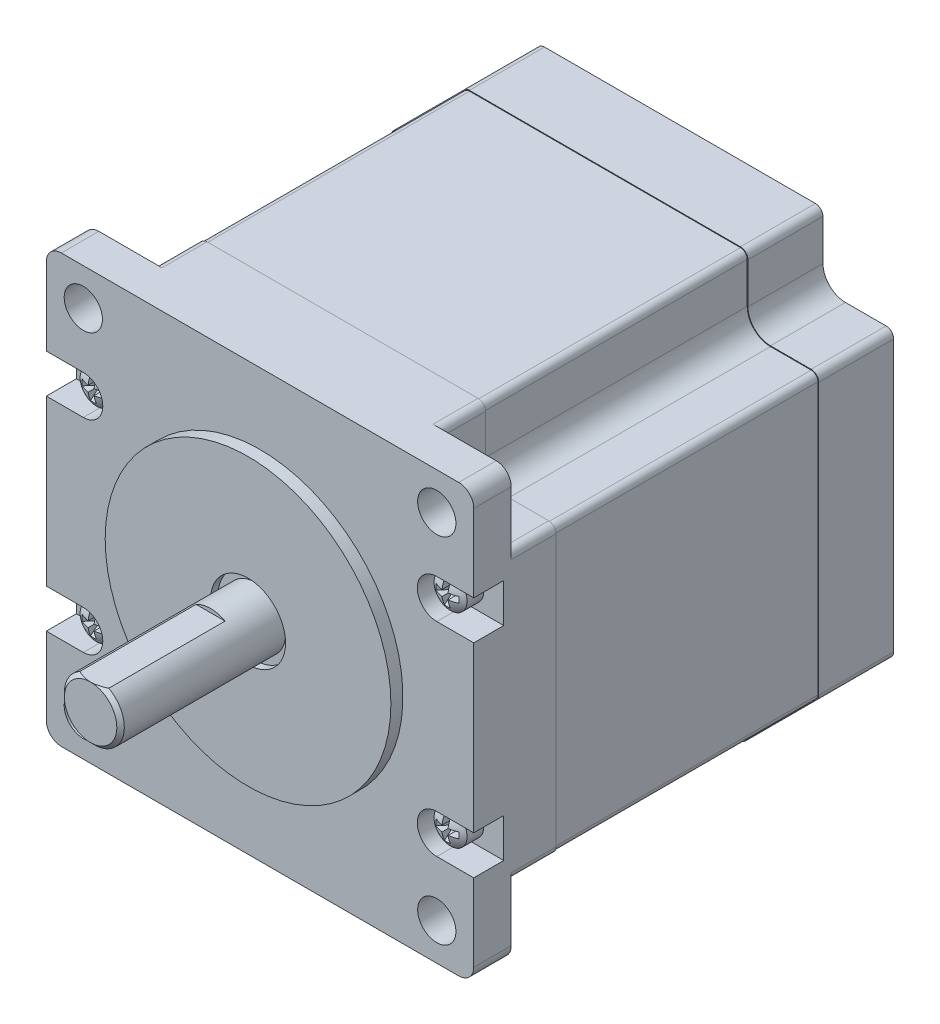
SolidWorks part; units mm, degrees
material "Liga 1060"
ref_plane "Plano frontal" through (0, 0, 0) normal (0, 0, 1) x (1, 0, 0)
ref_plane "Plano superior" through (0, 0, 0) normal (0, 1, 0) x (1, 0, 0)
ref_plane "Plano direito" through (0, 0, 0) normal (1, 0, 0) x (0, 0, -1)
sketch "Esboço1" plane through (0, 0, 0) normal (0, 0, 1) x (1, 0, 0)
  line L1 (-26.5, -28.5) -> (26.5, -28.5)
  line L2 (-28.5, -26.5) -> (-28.5, 26.5)
  line L3 (-26.5, 28.5) -> (26.5, 28.5)
  line L4 (28.5, -26.5) -> (28.5, 26.5)
  line L5 (-28.5, -28.5) -> (28.5, 28.5) construction
  line L6 (-28.5, 28.5) -> (28.5, -28.5) construction
  arc A0 (-26.5, -28.5) -> (-28.5, -26.5) centre (-26.5, -26.5) cw
  arc A1 (26.5, -28.5) -> (28.5, -26.5) centre (26.5, -26.5) ccw
  arc A2 (26.5, 28.5) -> (28.5, 26.5) centre (26.5, 26.5) cw
  arc A3 (-28.5, 26.5) -> (-26.5, 28.5) centre (-26.5, 26.5) cw
  point P0 (0, 0)
  dimension "D1" = 2
  dimension "D2" = 57
extrude "Ressalto-extrusão1" add sketch "Esboço1" along normal blind 5
sketch "Esboço2" plane through (0, 0, 5) normal (0, 0, 1) x (1, 0, 0)
  line L0 (-28.5, 0) -> (0, 0) construction
  line L1 (-28.5, 26.5) -> (-28.5, -26.5) construction
  line L2 (0, 0) -> (0, -28.5) construction
  line L3 (-26.5, -28.5) -> (26.5, -28.5) construction
  circle A0 centre (-23.57, -23.57) radius 2.55
  circle A1 centre (-23.57, 23.57) radius 2.55
  circle A2 centre (23.57, 23.57) radius 2.55
  circle A3 centre (23.57, -23.57) radius 2.55
  dimension "D1" = 47.14
  dimension "D2" = 47.14
  dimension "D3" = 5.1
extrude "Corte-extrusão1" cut sketch "Esboço2" against normal through all
sketch "Esboço4" plane through (0, 0, 0) normal (0, 0, -1) x (-1, 0, 0)
  line L0 (-28.5, 18.07) -> (-28.5, -18.07)
  line L1 (-27.5, -19.07) -> (-22.07, -19.07)
  line L2 (-19.07, -22.07) -> (-19.07, -27.5)
  line L3 (-18.07, -28.5) -> (18.07, -28.5)
  line L4 (0, -28.5) -> (0, 0) construction
  line L5 (0, 0) -> (-28.5, 0) construction
  line L6 (-28.5, -26.5) -> (-28.5, 26.5) construction
  line L7 (26.5, -28.5) -> (-26.5, -28.5) construction
  line L8 (-18.07, 28.5) -> (18.07, 28.5)
  line L9 (-19.07, 22.07) -> (-19.07, 27.5)
  line L10 (-27.5, 19.07) -> (-22.07, 19.07)
  line L11 (27.5, 19.07) -> (22.07, 19.07)
  line L12 (19.07, 22.07) -> (19.07, 27.5)
  line L13 (19.07, -22.07) -> (19.07, -27.5)
  line L14 (27.5, -19.07) -> (22.07, -19.07)
  line L15 (28.5, 18.07) -> (28.5, -18.07)
  arc A0 (-28.5, -18.07) -> (-27.5, -19.07) centre (-27.5, -18.07) ccw
  arc A1 (-22.07, -19.07) -> (-19.07, -22.07) centre (-22.07, -22.07) cw
  arc A2 (-19.07, -27.5) -> (-18.07, -28.5) centre (-18.07, -27.5) ccw
  circle A3 centre (-23.57, -23.57) radius 2.55 construction
  arc A4 (-19.07, 27.5) -> (-18.07, 28.5) centre (-18.07, 27.5) cw
  arc A5 (-22.07, 19.07) -> (-19.07, 22.07) centre (-22.07, 22.07) ccw
  arc A6 (-28.5, 18.07) -> (-27.5, 19.07) centre (-27.5, 18.07) cw
  arc A7 (28.5, 18.07) -> (27.5, 19.07) centre (27.5, 18.07) ccw
  arc A8 (22.07, 19.07) -> (19.07, 22.07) centre (22.07, 22.07) cw
  arc A9 (19.07, 27.5) -> (18.07, 28.5) centre (18.07, 27.5) ccw
  arc A10 (19.07, -27.5) -> (18.07, -28.5) centre (18.07, -27.5) cw
  arc A11 (22.07, -19.07) -> (19.07, -22.07) centre (22.07, -22.07) ccw
  arc A12 (28.5, -18.07) -> (27.5, -19.07) centre (27.5, -18.07) cw
  point P47 (0, 28.5)
  dimension "D1" = 4.5
  dimension "D2" = 4.5
  dimension "D3" = 3
  dimension "D4" = 1
extrude "Ressalto-extrusão2" add sketch "Esboço4" along normal blind 6
sketch "Esboço5" plane through (0, 0, 5) normal (0, 0, 1) x (1, 0, 0)
  line L0 (-28.5, -10.97) -> (-23.57, -10.97)
  line L1 (-28.5, 26.5) -> (-28.5, -26.5) construction
  line L2 (-23.57, -16.17) -> (-28.5, -16.17)
  line L3 (-28.5, -16.17) -> (-28.5, -10.97)
  line L4 (-23.57, -23.57) -> (-23.57, -13.57) construction
  line L5 (0, 0) -> (-28.5, 0) construction
  line L6 (0, 0) -> (0, -28.5) construction
  line L7 (-26.5, -28.5) -> (26.5, -28.5) construction
  line L8 (-28.5, 16.17) -> (-28.5, 10.97)
  line L9 (-23.57, 16.17) -> (-28.5, 16.17)
  line L10 (-28.5, 10.97) -> (-23.57, 10.97)
  line L11 (28.5, 10.97) -> (23.57, 10.97)
  line L12 (23.57, 16.17) -> (28.5, 16.17)
  line L13 (28.5, 16.17) -> (28.5, 10.97)
  line L14 (28.5, -16.17) -> (28.5, -10.97)
  line L15 (23.57, -16.17) -> (28.5, -16.17)
  line L16 (28.5, -10.97) -> (23.57, -10.97)
  arc A0 (-23.57, -10.97) -> (-23.57, -16.17) centre (-23.57, -13.57) cw
  arc A1 (-23.57, 10.97) -> (-23.57, 16.17) centre (-23.57, 13.57) ccw
  arc A2 (23.57, 10.97) -> (23.57, 16.17) centre (23.57, 13.57) cw
  arc A3 (23.57, -10.97) -> (23.57, -16.17) centre (23.57, -13.57) ccw
  dimension "D1" = 2.6
  dimension "D2" = 10
extrude "Corte-extrusão2" cut sketch "Esboço5" against normal blind 4
ref_plane "Plano1" through (-23.57, 0, 0) normal (1, 0, 0) x (0, 0, -1)
ref_axis "Eixo1" through (-23.57, 13.57, 1) along (0, 0, 1)
sketch "Esboço6" plane through (-23.57, 0, 0) normal (1, 0, 0) x (0, 0, -1)
  line L0 (-1, 15.77) -> (-3.2221, 15.77)
  line L1 (-1, 16.17) -> (-1, 10.97) construction
  line L2 (-1, 13.57) -> (-5, 13.57) construction
  line L3 (-1, 15.77) -> (-1, 13.57)
  line L4 (-1, 13.57) -> (-4, 13.57)
  arc A0 (-3.2221, 15.77) -> (-4, 13.57) centre (-0.5, 13.57) ccw
  dimension "D1" = 3.5
  dimension "D2" = 3
  dimension "D3" = 2.2
revolve "Revolução1" add sketch "Esboço6" angle 360 about L4
sketch "Esboço7" plane through (-23.57, 0, 0) normal (1, 0, 0) x (0, 0, -1)
  line L0 (-3.6469, 15.1021) -> (-2.2, 13.888)
  line L1 (-1, 13.57) -> (-5, 13.57) construction
  line L2 (-2.2, 13.252) -> (-3.6469, 12.0379)
  line L3 (-2.2, 13.252) -> (-2.2, 13.888)
  line L4 (-1, 16.17) -> (-1, 10.97) construction
  arc A0 (-3.2221, 15.77) -> (-3.2221, 11.37) centre (-0.5, 13.57) ccw construction
  arc A1 (-3.6469, 12.0379) -> (-3.6469, 15.1021) centre (-4.9324, 13.57) cw
  point P12 (-2.2, 13.57)
  dimension "D2" = 2
  dimension "D1" = 280
  dimension "D4" = 1.2
extrude "Corte-extrusão3" cut sketch "Esboço7" against normal blind 0.4 and the other way blind 0.4
pattern_circular "PadrãoCircular1" count 2 over 90 about axis through (-23.57, 13.57, 1) along (0, 0, -1) of "Corte-extrusão3"
pattern_linear "Padrão linear1" count 2 spacing 27.2 along (0, -1, 0) count 2 spacing 47.2 along (1, 0, 0) of "Revolução1", "Corte-extrusão3", "PadrãoCircular1"
sketch "Esboço8" plane through (0, 0, -6) normal (0, 0, -1) x (-1, 0, 0)
  line L0 (-27.5, -18.97) -> (-22.07, -18.97)
  line L1 (-18.97, -22.07) -> (-18.97, -27.5)
  line L2 (-18.07, -28.4) -> (18.07, -28.4)
  line L3 (18.97, -27.5) -> (18.97, -22.07)
  line L4 (22.07, -18.97) -> (27.5, -18.97)
  line L5 (28.4, -18.07) -> (28.4, 18.07)
  line L6 (27.5, 18.97) -> (22.07, 18.97)
  line L7 (18.97, 22.07) -> (18.97, 27.5)
  line L8 (18.07, 28.4) -> (-18.07, 28.4)
  line L9 (-18.97, 27.5) -> (-18.97, 22.07)
  line L10 (-22.07, 18.97) -> (-27.5, 18.97)
  line L11 (-28.4, 18.07) -> (-28.4, -18.07)
  line L12 (-27.5, -19.07) -> (-22.07, -19.07)
  line L13 (-19.07, -22.07) -> (-19.07, -27.5)
  line L14 (-18.07, -28.5) -> (18.07, -28.5)
  line L15 (19.07, -27.5) -> (19.07, -22.07)
  line L16 (22.07, -19.07) -> (27.5, -19.07)
  line L17 (28.5, -18.07) -> (28.5, 18.07)
  line L18 (27.5, 19.07) -> (22.07, 19.07)
  line L19 (19.07, 22.07) -> (19.07, 27.5)
  line L20 (18.07, 28.5) -> (-18.07, 28.5)
  line L21 (-19.07, 27.5) -> (-19.07, 22.07)
  line L22 (-22.07, 19.07) -> (-27.5, 19.07)
  line L23 (-28.5, 18.07) -> (-28.5, -18.07)
  line L24 (-27.5, -19.07) -> (-22.07, -19.07) construction
  line L25 (-19.07, -22.07) -> (-19.07, -27.5) construction
  line L26 (-18.07, -28.5) -> (18.07, -28.5) construction
  line L27 (19.07, -27.5) -> (19.07, -22.07) construction
  line L28 (22.07, -19.07) -> (27.5, -19.07) construction
  line L29 (28.5, -18.07) -> (28.5, 18.07) construction
  line L30 (27.5, 19.07) -> (22.07, 19.07) construction
  line L31 (19.07, 22.07) -> (19.07, 27.5) construction
  line L32 (18.07, 28.5) -> (-18.07, 28.5) construction
  line L33 (-19.07, 27.5) -> (-19.07, 22.07) construction
  line L34 (-22.07, 19.07) -> (-27.5, 19.07) construction
  line L35 (-28.5, 18.07) -> (-28.5, -18.07) construction
  arc A0 (-28.4, -18.07) -> (-27.5, -18.97) centre (-27.5, -18.07) ccw
  arc A1 (-18.97, -22.07) -> (-22.07, -18.97) centre (-22.07, -22.07) ccw
  arc A2 (-18.97, -27.5) -> (-18.07, -28.4) centre (-18.07, -27.5) ccw
  arc A3 (18.07, -28.4) -> (18.97, -27.5) centre (18.07, -27.5) ccw
  arc A4 (22.07, -18.97) -> (18.97, -22.07) centre (22.07, -22.07) ccw
  arc A5 (27.5, -18.97) -> (28.4, -18.07) centre (27.5, -18.07) ccw
  arc A6 (28.4, 18.07) -> (27.5, 18.97) centre (27.5, 18.07) ccw
  arc A7 (18.97, 22.07) -> (22.07, 18.97) centre (22.07, 22.07) ccw
  arc A8 (18.97, 27.5) -> (18.07, 28.4) centre (18.07, 27.5) ccw
  arc A9 (-18.07, 28.4) -> (-18.97, 27.5) centre (-18.07, 27.5) ccw
  arc A10 (-22.07, 18.97) -> (-18.97, 22.07) centre (-22.07, 22.07) ccw
  arc A11 (-27.5, 18.97) -> (-28.4, 18.07) centre (-27.5, 18.07) ccw
  arc A12 (-28.5, -18.07) -> (-27.5, -19.07) centre (-27.5, -18.07) ccw
  arc A13 (-19.07, -22.07) -> (-22.07, -19.07) centre (-22.07, -22.07) ccw
  arc A14 (-19.07, -27.5) -> (-18.07, -28.5) centre (-18.07, -27.5) ccw
  arc A15 (18.07, -28.5) -> (19.07, -27.5) centre (18.07, -27.5) ccw
  arc A16 (22.07, -19.07) -> (19.07, -22.07) centre (22.07, -22.07) ccw
  arc A17 (27.5, -19.07) -> (28.5, -18.07) centre (27.5, -18.07) ccw
  arc A18 (28.5, 18.07) -> (27.5, 19.07) centre (27.5, 18.07) ccw
  arc A19 (19.07, 22.07) -> (22.07, 19.07) centre (22.07, 22.07) ccw
  arc A20 (19.07, 27.5) -> (18.07, 28.5) centre (18.07, 27.5) ccw
  arc A21 (-18.07, 28.5) -> (-19.07, 27.5) centre (-18.07, 27.5) ccw
  arc A22 (-22.07, 19.07) -> (-19.07, 22.07) centre (-22.07, 22.07) ccw
  arc A23 (-27.5, 19.07) -> (-28.5, 18.07) centre (-27.5, 18.07) ccw
  arc A24 (-28.5, -18.07) -> (-27.5, -19.07) centre (-27.5, -18.07) ccw construction
  arc A25 (-19.07, -22.07) -> (-22.07, -19.07) centre (-22.07, -22.07) ccw construction
  arc A26 (-19.07, -27.5) -> (-18.07, -28.5) centre (-18.07, -27.5) ccw construction
  arc A27 (18.07, -28.5) -> (19.07, -27.5) centre (18.07, -27.5) ccw construction
  arc A28 (22.07, -19.07) -> (19.07, -22.07) centre (22.07, -22.07) ccw construction
  arc A29 (27.5, -19.07) -> (28.5, -18.07) centre (27.5, -18.07) ccw construction
  arc A30 (28.5, 18.07) -> (27.5, 19.07) centre (27.5, 18.07) ccw construction
  arc A31 (19.07, 22.07) -> (22.07, 19.07) centre (22.07, 22.07) ccw construction
  arc A32 (19.07, 27.5) -> (18.07, 28.5) centre (18.07, 27.5) ccw construction
  arc A33 (-18.07, 28.5) -> (-19.07, 27.5) centre (-18.07, 27.5) ccw construction
  arc A34 (-22.07, 19.07) -> (-19.07, 22.07) centre (-22.07, 22.07) ccw construction
  arc A35 (-27.5, 19.07) -> (-28.5, 18.07) centre (-27.5, 18.07) ccw construction
  dimension "D1" = 0
  dimension "D2" = 0.1
extrude "Ressalto-extrusão3" add sketch "Esboço8" along normal blind 35
sketch "Esboço9" plane through (0, 0, -41) normal (0, 0, -1) x (-1, 0, 0)
  line L24 (-27.5, -19.07) -> (-22.07, -19.07)
  line L25 (-19.07, -22.07) -> (-19.07, -27.5)
  line L26 (-18.07, -28.5) -> (18.07, -28.5)
  line L27 (19.07, -27.5) -> (19.07, -22.07)
  line L28 (22.07, -19.07) -> (27.5, -19.07)
  line L29 (28.5, -18.07) -> (28.5, 18.07)
  line L30 (27.5, 19.07) -> (22.07, 19.07)
  line L31 (19.07, 22.07) -> (19.07, 27.5)
  line L32 (18.07, 28.5) -> (-18.07, 28.5)
  line L33 (-19.07, 27.5) -> (-19.07, 22.07)
  line L34 (-22.07, 19.07) -> (-27.5, 19.07)
  line L35 (-28.5, 18.07) -> (-28.5, -18.07)
  line L36 (-27.5, -19.07) -> (-22.07, -19.07)
  line L37 (-19.07, -22.07) -> (-19.07, -27.5)
  line L38 (-18.07, -28.5) -> (18.07, -28.5)
  line L39 (19.07, -27.5) -> (19.07, -22.07)
  line L40 (22.07, -19.07) -> (27.5, -19.07)
  line L41 (28.5, -18.07) -> (28.5, 18.07)
  line L42 (27.5, 19.07) -> (22.07, 19.07)
  line L43 (19.07, 22.07) -> (19.07, 27.5)
  line L44 (18.07, 28.5) -> (-18.07, 28.5)
  line L45 (-19.07, 27.5) -> (-19.07, 22.07)
  line L46 (-22.07, 19.07) -> (-27.5, 19.07)
  line L47 (-28.5, 18.07) -> (-28.5, -18.07)
  arc A24 (-28.5, -18.07) -> (-27.5, -19.07) centre (-27.5, -18.07) ccw
  arc A25 (-19.07, -22.07) -> (-22.07, -19.07) centre (-22.07, -22.07) ccw
  arc A26 (-19.07, -27.5) -> (-18.07, -28.5) centre (-18.07, -27.5) ccw
  arc A27 (18.07, -28.5) -> (19.07, -27.5) centre (18.07, -27.5) ccw
  arc A28 (22.07, -19.07) -> (19.07, -22.07) centre (22.07, -22.07) ccw
  arc A29 (27.5, -19.07) -> (28.5, -18.07) centre (27.5, -18.07) ccw
  arc A30 (28.5, 18.07) -> (27.5, 19.07) centre (27.5, 18.07) ccw
  arc A31 (19.07, 22.07) -> (22.07, 19.07) centre (22.07, 22.07) ccw
  arc A32 (19.07, 27.5) -> (18.07, 28.5) centre (18.07, 27.5) ccw
  arc A33 (-18.07, 28.5) -> (-19.07, 27.5) centre (-18.07, 27.5) ccw
  arc A34 (-22.07, 19.07) -> (-19.07, 22.07) centre (-22.07, 22.07) ccw
  arc A35 (-27.5, 19.07) -> (-28.5, 18.07) centre (-27.5, 18.07) ccw
  arc A36 (-28.5, -18.07) -> (-27.5, -19.07) centre (-27.5, -18.07) ccw
  arc A37 (-19.07, -22.07) -> (-22.07, -19.07) centre (-22.07, -22.07) ccw
  arc A38 (-19.07, -27.5) -> (-18.07, -28.5) centre (-18.07, -27.5) ccw
  arc A39 (18.07, -28.5) -> (19.07, -27.5) centre (18.07, -27.5) ccw
  arc A40 (22.07, -19.07) -> (19.07, -22.07) centre (22.07, -22.07) ccw
  arc A41 (27.5, -19.07) -> (28.5, -18.07) centre (27.5, -18.07) ccw
  arc A42 (28.5, 18.07) -> (27.5, 19.07) centre (27.5, 18.07) ccw
  arc A43 (19.07, 22.07) -> (22.07, 19.07) centre (22.07, 22.07) ccw
  arc A44 (19.07, 27.5) -> (18.07, 28.5) centre (18.07, 27.5) ccw
  arc A45 (-18.07, 28.5) -> (-19.07, 27.5) centre (-18.07, 27.5) ccw
  arc A46 (-22.07, 19.07) -> (-19.07, 22.07) centre (-22.07, 22.07) ccw
  arc A47 (-27.5, 19.07) -> (-28.5, 18.07) centre (-27.5, 18.07) ccw
  dimension "D1" = 0
extrude "Ressalto-extrusão4" add sketch "Esboço9" along normal blind 10
sketch "Esboço10" plane through (0, 0, 5) normal (0, 0, 1) x (1, 0, 0)
  line L0 (0, 28.5) -> (0, -28.5) construction
  line L1 (26.5, 28.5) -> (-26.5, 28.5) construction
  line L2 (-26.5, -28.5) -> (26.5, -28.5) construction
  line L3 (-28.5, 0) -> (28.5, 0) construction
  line L4 (-28.5, 10.97) -> (-28.5, -10.97) construction
  line L5 (28.5, -10.97) -> (28.5, 10.97) construction
  circle A0 centre (0, 0) radius 19.05
  dimension "D1" = 38.1
extrude "Ressalto-extrusão5" add sketch "Esboço10" along normal blind 1.6
sketch "Esboço11" plane through (0, 0, 6.6) normal (0, 0, 1) x (1, 0, 0)
  circle A0 centre (0, 0) radius 5
  dimension "D1" = 10
extrude "Corte-extrusão4" cut sketch "Esboço11" against normal blind 1
sketch "Esboço12" plane through (0, 0, 5.6) normal (0, 0, 1) x (1, 0, 0)
  circle A0 centre (0, 0) radius 4
  dimension "D1" = 8
extrude "Ressalto-extrusão6" add sketch "Esboço12" along normal blind 22
chamfer "Chanfro1" distance 0.5 angle 45 1 edges at (4, 0, 27.6)
sketch "Esboço13" plane through (0, 0, 27.6) normal (0, 0, 1) x (1, 0, 0)
  line L0 (-1.9365, 3.5) -> (1.9365, 3.5)
  circle A0 centre (0, 0) radius 4 construction
  arc A1 (1.9365, 3.5) -> (-1.9365, 3.5) centre (0, 0) ccw
  dimension "D1" = 3.5
extrude "Corte-extrusão5" cut sketch "Esboço13" against normal blind 16
sketch "Esboço14" plane through (0, 0, -51) normal (0, 0, -1) x (-1, 0, 0)
  circle A0 centre (0, 0) radius 5
  circle A1 centre (0, 0) radius 4
  circle A2 centre (0, 0) radius 5 construction
  circle A3 centre (0, 0) radius 4 construction
extrude "Corte-extrusão6" cut sketch "Esboço14" against normal blind 1.5
